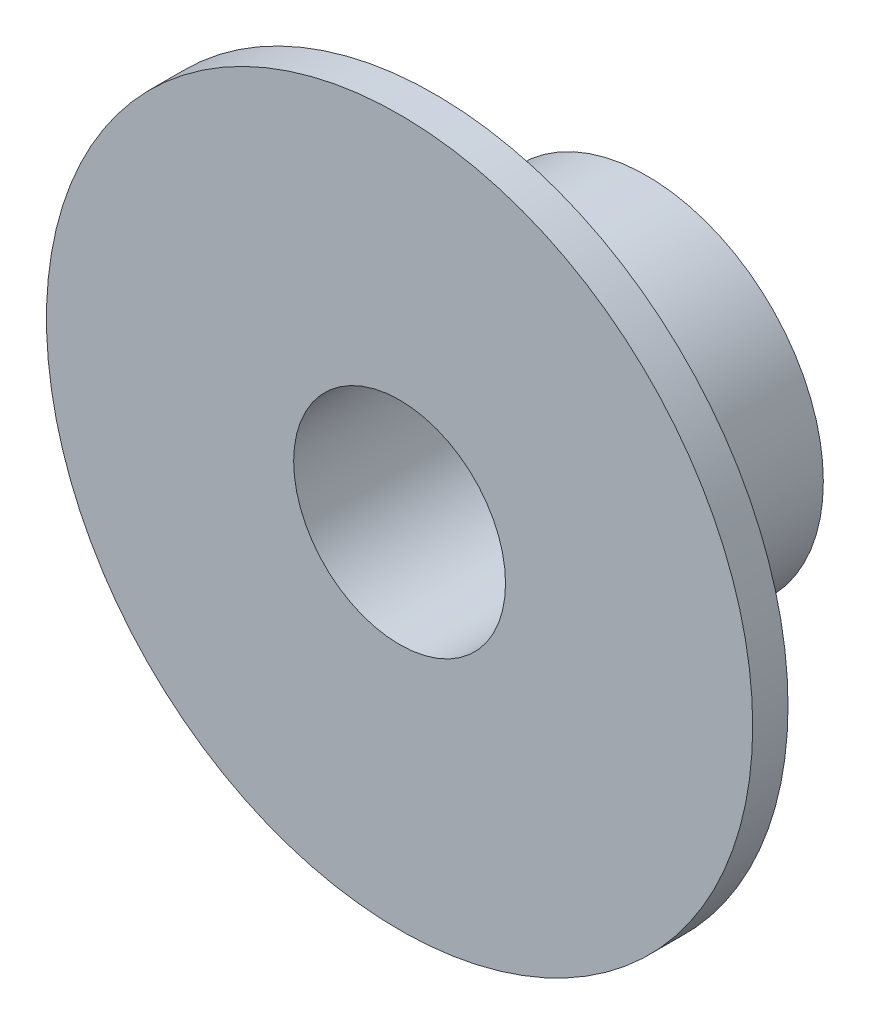
SolidWorks part; units mm, degrees
material "ABS"
ref_plane "Front Plane" through (0, 0, 0) normal (0, 0, 1) x (1, 0, 0)
ref_plane "Top Plane" through (0, 0, 0) normal (0, 1, 0) x (1, 0, 0)
ref_plane "Right Plane" through (0, 0, 0) normal (1, 0, 0) x (0, 0, -1)
sketch "Sketch1" plane through (0, 0, 0) normal (0, 0, 1) x (1, 0, 0)
  circle A0 centre (0, 0) radius 4.7625
  circle A1 centre (0, 0) radius 15.875
  dimension "D1" = 9.525
  dimension "D2" = 31.75
extrude "Boss-Extrude1" add sketch "Sketch1" along normal blind 1.5875
sketch "Sketch2" plane through (0, 0, 0) normal (0, 0, -1) x (-1, 0, 0)
  circle A0 centre (0, 0) radius 7.9375
  circle A1 centre (0, 0) radius 4.7625 construction
  circle A2 centre (0, 0) radius 4.7625
  dimension "D1" = 15.875
extrude "Boss-Extrude2" add sketch "Sketch2" along normal blind 9.525
